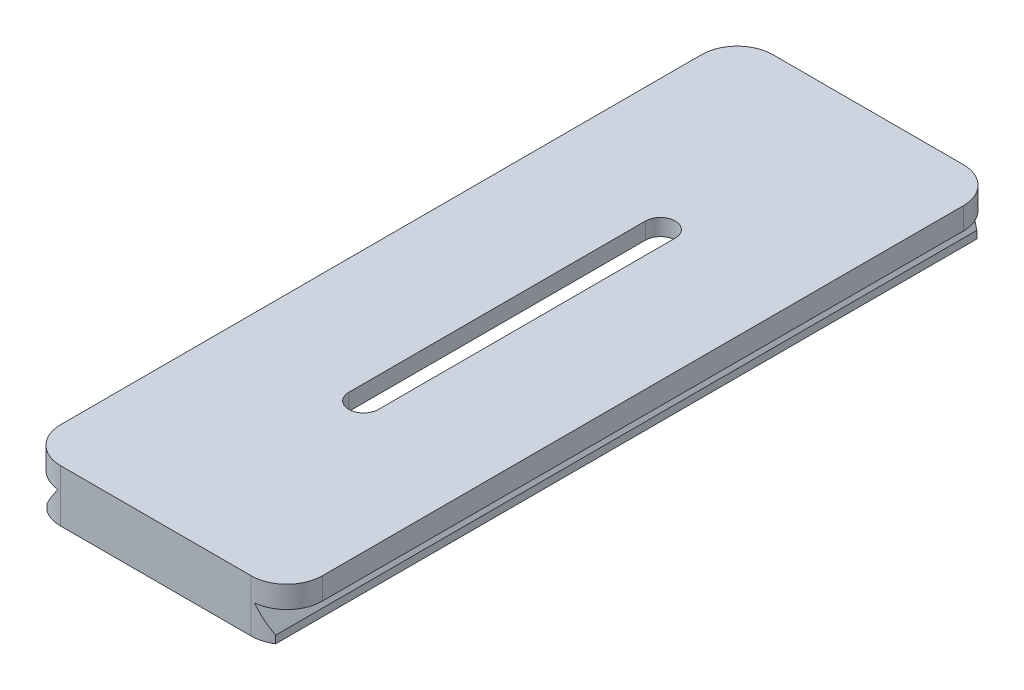
SolidWorks part; units mm, degrees
ref_plane "Front Plane" through (0, 0, 0) normal (0, 0, 1) x (1, 0, 0)
ref_plane "Top Plane" through (0, 0, 0) normal (0, 1, 0) x (1, 0, 0)
ref_plane "Right Plane" through (0, 0, 0) normal (1, 0, 0) x (0, 0, -1)
sketch "Sketch1" plane through (0, 0, 0) normal (0, 1, 0) x (1, 0, 0)
  line L0 (0, -25) -> (0, 25) construction
  line L1 (-22.05, -60) -> (22.05, -60)
  line L2 (-22.05, -60) -> (-22.05, 60)
  line L3 (-22.05, 60) -> (22.05, 60)
  line L4 (22.05, -60) -> (22.05, 60)
  line L5 (-22.05, -60) -> (22.05, 60) construction
  line L6 (-22.05, 60) -> (22.05, -60) construction
  line L7 (-2.5, -25) -> (-2.5, 25)
  line L8 (2.5, -25) -> (2.5, 25)
  arc A0 (-2.5, -25) -> (2.5, -25) centre (0, -25) ccw
  arc A1 (2.5, 25) -> (-2.5, 25) centre (0, 25) ccw
  point P0 (0, 0)
  point P8 (0, 0)
  dimension "D1" = 44.1
  dimension "D2" = 120
  dimension "D3" = 50
  dimension "D4" = 5
extrude "Boss-Extrude1" add sketch "Sketch1" along normal blind 8.8
fillet "Fillet1" radius 6 4 edges at (-22.05, 4.4, 60) (-22.05, 4.4, -60) (22.05, 4.4, -60) (22.05, 4.4, 60)
sketch "Sketch2" plane through (0, 0, 60) normal (0, 0, 1) x (1, 0, 0)
  line L0 (19.25, 0) -> (19.25, 1.2703)
  line L2 (16.05, 0) -> (22.05, 0) construction
  line L3 (19.25, 1.2703) -> (16.65, 4.9584)
  line L4 (16.65, 4.9584) -> (16.65, 5.1)
  line L5 (16.65, 5.1) -> (22.05, 5.1)
  line L6 (22.05, 8.8) -> (22.05, 0) construction
  line L7 (22.05, 5.1) -> (22.05, 0)
  line L8 (22.05, 0) -> (19.25, 0)
  line L9 (0, 0) -> (0, 8.8) construction
  line L10 (-16.05, 8.8) -> (16.05, 8.8) construction
  line L11 (22.05, 8.8) -> (16.05, 8.8) construction
  line L12 (-22.05, 0) -> (-19.25, 0)
  line L13 (-22.05, 5.1) -> (-22.05, 0)
  line L14 (-16.65, 5.1) -> (-22.05, 5.1)
  line L15 (-16.65, 4.9584) -> (-16.65, 5.1)
  line L16 (-19.25, 1.2703) -> (-16.65, 4.9584)
  line L17 (-19.25, 0) -> (-19.25, 1.2703)
  dimension "D1" = 38.5
  dimension "D2" = 33.3
  dimension "D3" = 3.7
extrude "Cut-Extrude1" cut sketch "Sketch2" against normal through all
sketch "Sketch3" plane through (0, 0, 0) normal (0, -1, 0) x (1, 0, 0)
  line L0 (19.25, -59.0754) -> (19.25, 59.0754) construction
  line L1 (-8.95, -55) -> (8.95, -55)
  line L2 (-13.95, -50) -> (-13.95, 50)
  line L3 (-8.95, 55) -> (8.95, 55)
  line L4 (13.95, -50) -> (13.95, 50)
  line L5 (-13.95, -55) -> (13.95, 55) construction
  line L6 (-13.95, 55) -> (13.95, -55) construction
  line L7 (-16.05, 60) -> (16.05, 60) construction
  arc A0 (-13.95, -50) -> (-8.95, -55) centre (-8.95, -50) ccw
  arc A1 (8.95, -55) -> (13.95, -50) centre (8.95, -50) ccw
  arc A2 (-13.95, 50) -> (-8.95, 55) centre (-8.95, 50) cw
  arc A3 (13.95, 50) -> (8.95, 55) centre (8.95, 50) ccw
  point P0 (0, 0)
  dimension "D3" = 5
  dimension "D1" = 5.3
  dimension "D2" = 5
extrude "Cut-Extrude2" cut sketch "Sketch3" against normal blind 6
